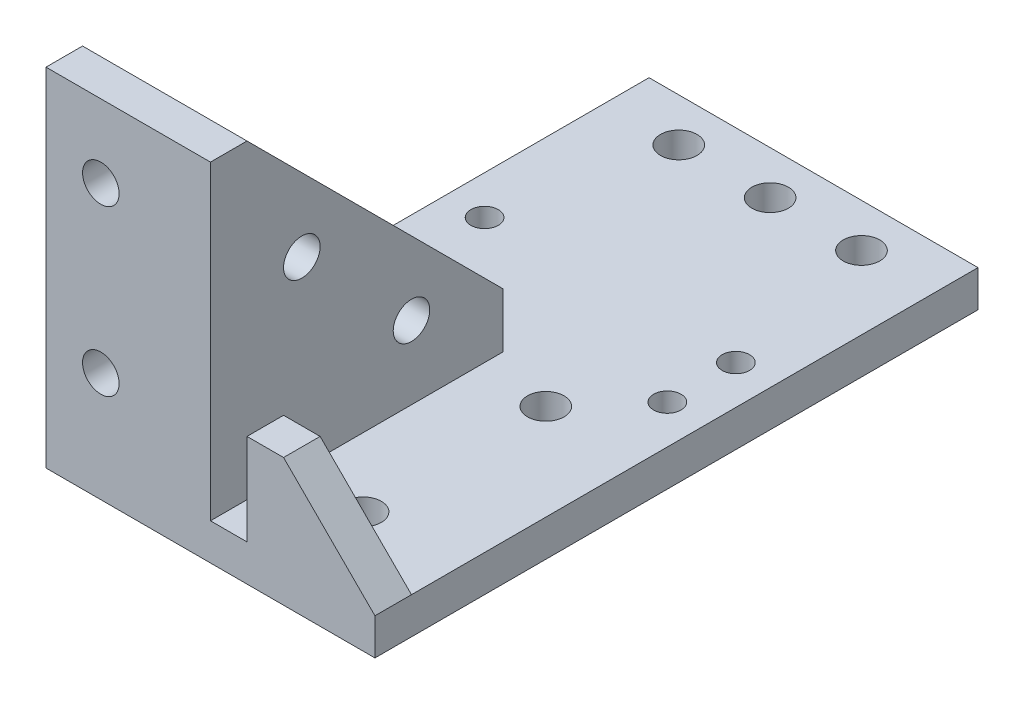
SolidWorks part; units mm, degrees
ref_plane "Front Plane" through (0, 0, 0) normal (0, 0, 1) x (1, 0, 0)
ref_plane "Top Plane" through (0, 0, 0) normal (0, 1, 0) x (1, 0, 0)
ref_plane "Right Plane" through (0, 0, 0) normal (1, 0, 0) x (0, 0, -1)
sketch "Sketch1" plane through (0, 0, 0) normal (0, 1, 0) x (1, 0, 0)
  line L0 (0, 108.3742) -> (0, -10.7395) construction
  line L1 (-51.4374, 0) -> (47.9292, 0) construction
  line L6 (-18, 66) -> (18, 66)
  line L7 (-18, 66) -> (-18, 6)
  line L9 (18, 66) -> (18, 6)
  line L10 (-18, 66) -> (18, 6) construction
  line L11 (-18, 6) -> (18, 66) construction
  line L12 (-18, 0) -> (18, 0)
  line L16 (-18, 6) -> (-18, 0)
  line L17 (18, 6) -> (18, 0)
  line L19 (-21.5962, 6) -> (41.0349, 6) construction
  point P3 (0, 36)
  dimension "D1" = 36
  dimension "D2" = 60
  dimension "D3" = 6
extrude "Boss-Extrude1" add sketch "Sketch1" along normal blind 4
sketch "Sketch2" plane through (0, 4, 0) normal (0, 1, 0) x (1, 0, 0)
  line L0 (-10, 61.25) -> (10, 61.25) construction
  line L1 (0, -14.7291) -> (0, 58.7438) construction
  line L2 (-13.75, 43.75) -> (13.75, 43.75) construction
  line L3 (-13.75, 43.75) -> (-13.75, 36.25) construction
  line L4 (-13.75, 36.25) -> (13.75, 36.25) construction
  line L5 (13.75, 43.75) -> (13.75, 36.25) construction
  line L6 (-13.75, 43.75) -> (13.75, 36.25) construction
  line L7 (-13.75, 36.25) -> (13.75, 43.75) construction
  line L8 (-7.5, 9.2) -> (7.5, 9.2) construction
  line L9 (-7.5, 9.2) -> (-7.5, 29.2) construction
  line L10 (-7.5, 29.2) -> (7.5, 29.2) construction
  line L11 (7.5, 9.2) -> (7.5, 29.2) construction
  line L12 (-7.5, 9.2) -> (7.5, 29.2) construction
  line L13 (-7.5, 29.2) -> (7.5, 9.2) construction
  line L16 (18, 66) -> (-18, 66) construction
  circle A0 centre (-10, 61.25) radius 2
  circle A1 centre (0, 61.25) radius 2
  circle A2 centre (10, 61.25) radius 2
  circle A3 centre (-7.5, 9.2) radius 2
  circle A4 centre (-7.5, 29.2) radius 2
  circle A5 centre (7.5, 29.2) radius 2
  circle A6 centre (7.5, 9.2) radius 2
  circle A7 centre (13.75, 36.25) radius 1.5
  circle A8 centre (13.75, 43.75) radius 1.5
  circle A9 centre (-13.75, 43.75) radius 1.5
  circle A10 centre (-13.75, 36.25) radius 1.5
  point P2 (0, 40)
  point P12 (0, 19.2)
  point P20 (0, 61.25)
  dimension "D10" = 4
  dimension "D11" = 4
  dimension "D12" = 3
  dimension "D1" = 20
  dimension "D2" = 15
  dimension "D3" = 46.8
  dimension "D4" = 7.5
  dimension "D5" = 27.5
  dimension "D6" = 26
  dimension "D7" = 4.75
  dimension "D8" = 20
  dimension "D9" = 10
extrude "Cut-Extrude1" cut sketch "Sketch2" against normal through all
ref_plane "Plane1" through (0, 0, 0) normal (1, 0, 0) x (0, 0, -1)
sketch "Sketch5" plane through (0, 0, 0) normal (1, 0, 0) x (0, 0, -1)
  line L0 (0, 4) -> (0, 38)
  line L1 (0, 38) -> (4, 38)
  line L2 (4, 38) -> (32, 10)
  line L3 (32, 10) -> (32, 4)
  line L4 (0, 4) -> (66, 4) construction
  line L5 (32, 4) -> (0, 4)
  dimension "D1" = 34
  dimension "D2" = 4
  dimension "D3" = 6
  dimension "D4" = 45
extrude "Boss-Extrude5" add sketch "Sketch5" against normal blind 4
sketch "Sketch6" plane through (0, 0, 0) normal (0, 0, 1) x (1, 0, 0)
  line L0 (-4, 38) -> (-18, 38)
  line L1 (-4, 38) -> (0, 38) construction
  line L2 (-4, 38) -> (-4, 4) construction
  line L3 (-18, 38) -> (-18, 4)
  line L4 (-18, 4) -> (-4, 4)
  line L5 (-4, 4) -> (-4, 38)
extrude "Boss-Extrude6" add sketch "Sketch6" against normal blind 4
sketch "Sketch7" plane through (0, 0, 0) normal (0, 0, 1) x (1, 0, 0)
  line L0 (4, 4) -> (4, 14)
  line L1 (0, 4) -> (18, 4) construction
  line L2 (4, 14) -> (8, 14)
  line L3 (8, 14) -> (18, 4)
  line L4 (0, 38) -> (0, 4) construction
  line L5 (4, 4) -> (18, 4)
  line L6 (18, 4) -> (18, 0) construction
  dimension "D1" = 4
  dimension "D2" = 4
  dimension "D3" = 45
extrude "Boss-Extrude7" add sketch "Sketch7" against normal blind 4
sketch "Sketch8" plane through (-4, 0, 0) normal (-1, 0, 0) x (0, 0, 1)
  line L0 (-32, 12) -> (-10, 12) construction
  line L1 (-10, 32) -> (-10, 12) construction
  line L2 (-4, 4) -> (-32, 4) construction
  line L3 (0, 38) -> (0, 0) construction
  circle A1 centre (-10, 24) radius 2
  circle A2 centre (-22, 12) radius 2
  dimension "D3" = 4
  dimension "D1" = 12
  dimension "D2" = 12
  dimension "D4" = 10
  dimension "D5" = 8
  dimension "D6" = 10
extrude "Cut-Extrude2" cut sketch "Sketch8" against normal through all
sketch "Sketch9" plane through (0, 0, -4) normal (0, 0, -1) x (-1, 0, 0)
  line L0 (12, 4.695) -> (12, 30.9324) construction
  line L1 (18, 38) -> (18, 4) construction
  line L2 (-18, 4) -> (18, 4) construction
  circle A0 centre (12, 12) radius 2
  circle A1 centre (12, 30) radius 2
  dimension "D4" = 4
  dimension "D1" = 6
  dimension "D2" = 18
  dimension "D3" = 8
extrude "Cut-Extrude3" cut sketch "Sketch9" against normal blind 4
fillet "Fillet1" [suppressed] radius 4
